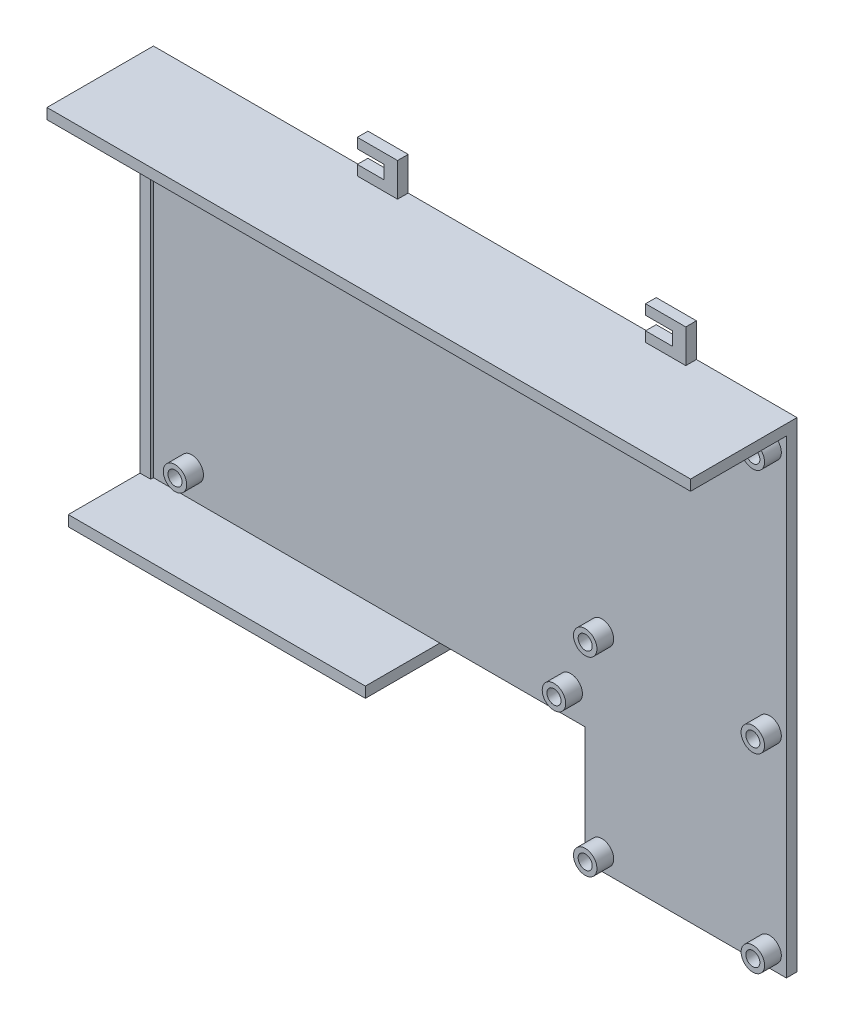
SolidWorks part; units mm, degrees
material "Custom Plastic"
ref_plane "X-Y Datum" through (0, 0, 0) normal (0, 0, 1) x (1, 0, 0)
ref_plane "X-Z Datum" through (0, 0, 0) normal (0, 1, 0) x (1, 0, 0)
ref_plane "Y-Z Datum" through (0, 0, 0) normal (1, 0, 0) x (0, 0, -1)
ref_plane "Plane1" through (-104.4093, 129.7126, 34.8019) normal (0, 1, 0) x (1, 0, 0)
sketch "Sketch2" plane through (0, 0, 32.7768) normal (0, 0, -1) x (-1, 0, 0)
  circle A0 centre (218.5263, 69.3586) radius 2.1 construction
  circle A1 centre (218.5263, 162.3226) radius 2.1 construction
  circle A2 centre (105.4963, 162.3226) radius 2.1 construction
  circle A3 centre (96.1783, 161.3866) radius 2.0955 construction
  circle A4 centre (105.4963, 69.3586) radius 2.1 construction
  circle A5 centre (96.1783, 88.1366) radius 2.0955 construction
  circle A6 centre (96.1783, 31.3866) radius 2.0955 construction
  circle A7 centre (46.1783, 31.3866) radius 2.0955 construction
  circle A8 centre (46.1783, 88.1366) radius 2.0955 construction
  circle A9 centre (46.1783, 161.3866) radius 2.0955 construction
  circle A10 centre (218.5263, 69.3586) radius 2.1
  circle A11 centre (218.5263, 162.3226) radius 2.1
  circle A12 centre (105.4963, 162.3226) radius 2.1
  circle A13 centre (96.1783, 161.3866) radius 2.0955
  circle A14 centre (105.4963, 69.3586) radius 2.1
  circle A15 centre (96.1783, 88.1366) radius 2.0955
  circle A16 centre (96.1783, 31.3866) radius 2.0955
  circle A17 centre (46.1783, 31.3866) radius 2.0955
  circle A18 centre (46.1783, 88.1366) radius 2.0955
  circle A19 centre (46.1783, 161.3866) radius 2.0955
  circle A20 centre (46.1783, 161.3866) radius 3.5
  circle A21 centre (96.1783, 161.3866) radius 3.5
  circle A22 centre (105.4963, 162.3226) radius 3.5
  circle A23 centre (218.5263, 162.3226) radius 3.5
  circle A24 centre (46.1783, 88.1366) radius 3.5
  circle A25 centre (46.1783, 31.3866) radius 3.5
  circle A26 centre (96.1783, 31.3866) radius 3.5
  circle A27 centre (96.1783, 88.1366) radius 3.5
  circle A28 centre (105.4963, 69.3586) radius 3.5
  circle A29 centre (218.5263, 69.3586) radius 3.5
  dimension "D1" = 7
  dimension "D2" = 7
  dimension "D3" = 7
  dimension "D4" = 7
extrude "Boss-Extrude1" add sketch "Sketch2" along normal blind 5
sketch "Sketch3" plane through (0, 0, 27.7768) normal (0, 0, -1) x (-1, 0, 0)
  line L1 (41.1783, 166.3866) -> (229.9563, 166.3866)
  line L2 (41.1783, 166.3866) -> (41.1783, 61.2306)
  line L3 (101.1783, 61.2306) -> (229.9563, 61.2306)
  line L4 (229.9563, 166.3866) -> (229.9563, 61.2306)
  line L6 (41.1783, 61.2306) -> (41.1783, 26.3866)
  line L7 (41.1783, 26.3866) -> (101.1783, 26.3866)
  line L8 (101.1783, 61.2306) -> (101.1783, 26.3866)
extrude "Boss-Extrude2" add sketch "Sketch3" along normal blind 3.175
sketch "Sketch4" plane through (0, 0, 24.6018) normal (0, 0, -1) x (-1, 0, 0)
  line L0 (41.1783, 166.3866) -> (41.1783, 169.5616)
  line L1 (144.5201, 58.0556) -> (144.5201, 61.2306)
  line L2 (101.1783, 61.2306) -> (229.9563, 61.2306) construction
  line L3 (229.9563, 166.3866) -> (233.1313, 166.3866)
  line L4 (229.9563, 61.2306) -> (233.1313, 61.2306)
  line L12 (38.0033, 169.5616) -> (38.0033, 23.2116)
  line L13 (38.0033, 23.2116) -> (104.3533, 23.2116)
  line L14 (104.3533, 23.2116) -> (104.3533, 58.0556)
  line L15 (104.3533, 58.0556) -> (233.1313, 58.0556)
  line L16 (233.1313, 58.0556) -> (233.1313, 169.5616)
  line L17 (233.1313, 169.5616) -> (38.0033, 169.5616)
  line L18 (38.0033, 169.5616) -> (38.0033, 23.2116)
  line L19 (38.0033, 23.2116) -> (104.3533, 23.2116)
  line L20 (104.3533, 23.2116) -> (104.3533, 58.0556)
  line L21 (104.3533, 58.0556) -> (233.1313, 58.0556)
  line L22 (233.1313, 58.0556) -> (233.1313, 169.5616)
  line L23 (233.1313, 169.5616) -> (38.0033, 169.5616)
  line M10 (101.1783, 61.2306) -> (229.9563, 61.2306)
  line M11 (229.9563, 61.2306) -> (229.9563, 166.3866)
  line M12 (229.9563, 166.3866) -> (41.1783, 166.3866)
  dimension "D1" = 3.175
extrude "Boss-Extrude3" add sketch "Sketch4" against normal blind 25.4 contours L22 L23 L18 L1 L21 M12 M11 M10 region at (-188.8257, 59.6431, 24.6018)
extrude "Boss-Extrude4" add sketch "Sketch4<3>" against normal blind 16 contours L21 L22 L4 L1 M10 region at (-188.8257, 59.6431, 24.6018)
sketch "Sketch4<3>" plane through (0, 0, 24.6018) normal (0, 0, -1) x (-1, 0, 0) same geometry as "Sketch4"
sketch "Sketch5" plane through (0, 0, 24.6018) normal (0, 0, -1) x (-1, 0, 0)
  line L0 (166.0515, 58.0556) -> (166.0515, 48.0556)
  line L1 (144.5201, 58.0556) -> (233.1313, 58.0556) construction
  line L2 (166.0515, 48.0556) -> (178.0515, 48.0556)
  line L3 (178.0515, 48.0556) -> (178.0515, 51.0556)
  line L4 (178.0515, 51.0556) -> (170.0515, 51.0556)
  line L5 (170.0515, 51.0556) -> (170.0515, 55.0556)
  line L6 (170.0515, 55.0556) -> (178.0515, 55.0556)
  line L7 (178.0515, 55.0556) -> (178.0515, 58.0556)
  line L8 (178.0515, 58.0556) -> (166.0515, 58.0556)
  line L9 (144.5201, 58.0556) -> (144.5201, 61.2306) construction
  dimension "D1" = 10
  dimension "D2" = 12
  dimension "D3" = 8
  dimension "D4" = 3
  dimension "D5" = 21.5314
extrude "Boss-Extrude5" add sketch "Sketch5" against normal blind 3.175
extrude "Boss-Extrude6" add sketch "Sketch4<4>" against normal blind 31.75 contours L22 L23 L0 L3 M12 region at (-137.1548, 167.9741, 24.6018)
sketch "Sketch4<4>" plane through (0, 0, 24.6018) normal (0, 0, -1) x (-1, 0, 0) same geometry as "Sketch4"
extrude "Boss-Extrude7" add sketch "Sketch4<5>" against normal blind 4 contours L4 L22 L3 M11 region at (-231.5438, 113.8086, 24.6018)
sketch "Sketch4<5>" plane through (0, 0, 24.6018) normal (0, 0, -1) x (-1, 0, 0) same geometry as "Sketch4"
sketch "Sketch6" plane through (0, 0, 24.6018) normal (0, 0, -1) x (-1, 0, 0)
  line L0 (137.1548, 169.5616) -> (137.1548, 61.2306)
  line L1 (233.1313, 169.5616) -> (41.1783, 169.5616) construction
  line L2 (101.1783, 61.2306) -> (144.5201, 61.2306) construction
  line L3 (157.1548, 169.5616) -> (157.1548, 179.5616)
  line L4 (157.1548, 179.5616) -> (169.1548, 179.5616)
  line L5 (169.1548, 179.5616) -> (169.1548, 176.5616)
  line L6 (169.1548, 176.5616) -> (161.1548, 176.5616)
  line L7 (161.1548, 176.5616) -> (161.1548, 172.5616)
  line L8 (161.1548, 172.5616) -> (169.1548, 172.5616)
  line L9 (169.1548, 172.5616) -> (169.1548, 169.5616)
  line L10 (169.1548, 169.5616) -> (157.1548, 169.5616)
  line L11 (71.1783, 179.5616) -> (71.1783, 169.5616)
  line L12 (71.1783, 169.5616) -> (83.1783, 169.5616)
  line L13 (83.1783, 169.5616) -> (83.1783, 172.5616)
  line L14 (83.1783, 172.5616) -> (75.1783, 172.5616)
  line L15 (75.1783, 172.5616) -> (75.1783, 176.5616)
  line L16 (75.1783, 176.5616) -> (83.1783, 176.5616)
  line L17 (83.1783, 176.5616) -> (83.1783, 179.5616)
  line L18 (83.1783, 179.5616) -> (71.1783, 179.5616)
  line L19 (41.1783, 169.5616) -> (41.1783, 26.3866) construction
  line M13 (233.1313, 169.5616) -> (41.1783, 169.5616)
  dimension "D1" = 30
  dimension "D2" = 3
  dimension "D3" = 10
  dimension "D4" = 12
  dimension "D5" = 8
  dimension "D6" = 20
  dimension "D7" = 12
  dimension "D8" = 8
  dimension "D9" = 10
  dimension "D10" = 3
extrude "Boss-Extrude8" add sketch "Sketch6" against normal blind 3.175 contours L17 L18 L11 L13 L14 L15 L16 M13 | L9 L8 L7 L6 L5 L4 L3 M13 region at (-157.311, 174.5616, 24.6018) region at (-77.1783, 169.7178, 24.6018)
equation "\"16mmm\"=20"
